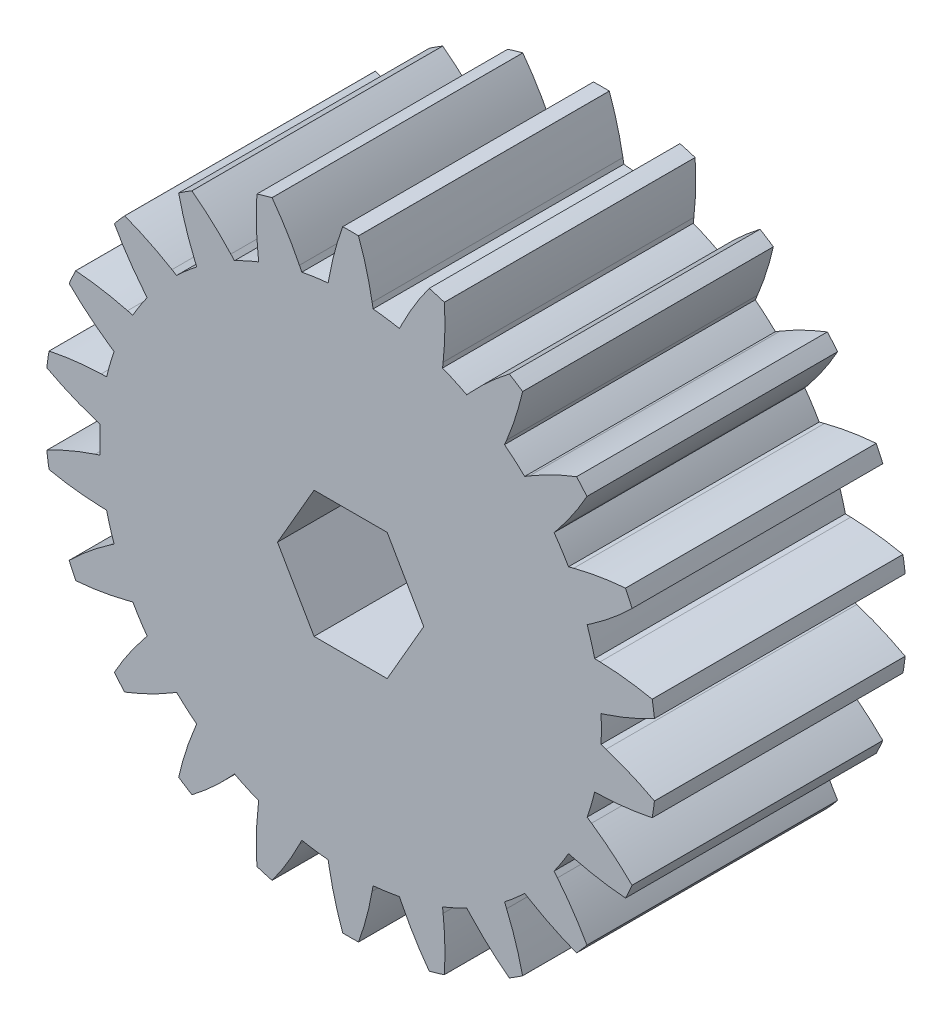
SolidWorks part; units mm, degrees
material "Custom Plastic"
ref_plane "Front Plane" through (0, 0, 0) normal (0, 0, 1) x (1, 0, 0)
ref_plane "Top Plane" through (0, 0, 0) normal (0, 1, 0) x (1, 0, 0)
ref_plane "Right Plane" through (0, 0, 0) normal (1, 0, 0) x (0, 0, -1)
sketch "Sketch1" plane through (0, 0, 0) normal (0, 0, 1) x (1, 0, 0)
  line L0 (0, 30.988) -> (0, 0) construction
  line L1 (-2.2733, 25.2981) -> (-1.27, 30.988)
  line L2 (-1.27, 30.988) -> (1.27, 30.988)
  line L3 (1.27, 30.988) -> (2.2733, 25.2981)
  line L4 (4.9461, 24.9138) -> (7.5118, 30.0906)
  line L5 (7.5118, 30.0906) -> (9.9489, 29.375)
  line L6 (9.9489, 29.375) -> (9.3085, 23.6329)
  line L7 (11.7648, 22.5111) -> (15.685, 26.7554)
  line L8 (15.685, 26.7554) -> (17.8218, 25.3822)
  line L9 (17.8218, 25.3822) -> (15.5896, 20.0531)
  line L10 (17.6303, 18.2847) -> (22.5875, 21.2526)
  line L11 (22.5875, 21.2526) -> (24.2508, 19.333)
  line L12 (24.2508, 19.333) -> (20.6077, 14.8487)
  line L13 (22.0676, 12.5771) -> (27.6601, 14.0281)
  line L14 (27.6601, 14.0281) -> (28.7153, 11.7176)
  line L15 (28.7153, 11.7176) -> (23.9563, 8.4413)
  line L16 (24.717, 5.8504) -> (30.4918, 5.6671)
  line L17 (30.4918, 5.6671) -> (30.8533, 3.153)
  line L18 (30.8533, 3.153) -> (25.3641, 1.3501)
  line L19 (25.3641, -1.3501) -> (30.8533, -3.153)
  line L20 (30.8533, -3.153) -> (30.4918, -5.6671)
  line L21 (30.4918, -5.6671) -> (24.717, -5.8504)
  line L22 (23.9563, -8.4413) -> (28.7153, -11.7176)
  line L23 (28.7153, -11.7176) -> (27.6601, -14.0281)
  line L24 (27.6601, -14.0281) -> (22.0676, -12.5771)
  line L25 (20.6077, -14.8487) -> (24.2508, -19.333)
  line L26 (24.2508, -19.333) -> (22.5875, -21.2526)
  line L27 (22.5875, -21.2526) -> (17.6303, -18.2847)
  line L28 (15.5896, -20.0531) -> (17.8218, -25.3822)
  line L29 (17.8218, -25.3822) -> (15.685, -26.7554)
  line L30 (15.685, -26.7554) -> (11.7648, -22.5111)
  line L31 (9.3085, -23.6329) -> (9.9489, -29.375)
  line L32 (9.9489, -29.375) -> (7.5118, -30.0906)
  line L33 (7.5118, -30.0906) -> (4.9461, -24.9138)
  line L34 (2.2733, -25.2981) -> (1.27, -30.988)
  line L35 (1.27, -30.988) -> (-1.27, -30.988)
  line L36 (-1.27, -30.988) -> (-2.2733, -25.2981)
  line L37 (-4.9461, -24.9138) -> (-7.5118, -30.0906)
  line L38 (-7.5118, -30.0906) -> (-9.9489, -29.375)
  line L39 (-9.9489, -29.375) -> (-9.3085, -23.6329)
  line L40 (-11.7648, -22.5111) -> (-15.685, -26.7554)
  line L41 (-15.685, -26.7554) -> (-17.8218, -25.3822)
  line L42 (-17.8218, -25.3822) -> (-15.5896, -20.0531)
  line L43 (-17.6303, -18.2847) -> (-22.5875, -21.2526)
  line L44 (-22.5875, -21.2526) -> (-24.2508, -19.333)
  line L45 (-24.2508, -19.333) -> (-20.6077, -14.8487)
  line L46 (-22.0676, -12.5771) -> (-27.6601, -14.0281)
  line L47 (-27.6601, -14.0281) -> (-28.7153, -11.7176)
  line L48 (-28.7153, -11.7176) -> (-23.9563, -8.4413)
  line L49 (-24.717, -5.8504) -> (-30.4918, -5.6671)
  line L50 (-30.4918, -5.6671) -> (-30.8533, -3.153)
  line L51 (-30.8533, -3.153) -> (-25.3641, -1.3501)
  line L52 (-25.3641, 1.3501) -> (-30.8533, 3.153)
  line L53 (-30.8533, 3.153) -> (-30.4918, 5.6671)
  line L54 (-30.4918, 5.6671) -> (-24.717, 5.8504)
  line L55 (-23.9563, 8.4413) -> (-28.7153, 11.7176)
  line L56 (-28.7153, 11.7176) -> (-27.6601, 14.0281)
  line L57 (-27.6601, 14.0281) -> (-22.0676, 12.5771)
  line L58 (-20.6077, 14.8487) -> (-24.2508, 19.333)
  line L59 (-24.2508, 19.333) -> (-22.5875, 21.2526)
  line L60 (-22.5875, 21.2526) -> (-17.6303, 18.2847)
  line L61 (-15.5896, 20.0531) -> (-17.8218, 25.3822)
  line L62 (-17.8218, 25.3822) -> (-15.685, 26.7554)
  line L63 (-15.685, 26.7554) -> (-11.7648, 22.5111)
  line L64 (-9.3085, 23.6329) -> (-9.9489, 29.375)
  line L65 (-9.9489, 29.375) -> (-7.5118, 30.0906)
  line L66 (-7.5118, 30.0906) -> (-4.9461, 24.9138)
  arc A0 (-25.3641, 1.3501) -> (-25.3641, -1.3501) centre (0, 0) ccw
  arc A1 (0, 30.988) -> (8.7303, 29.7328) centre (0, 0) cw construction
  arc A2 (-23.9563, 8.4413) -> (-24.717, 5.8504) centre (0, 0) ccw
  arc A3 (-20.6077, 14.8487) -> (-22.0676, 12.5771) centre (0, 0) ccw
  arc A4 (-15.5896, 20.0531) -> (-17.6303, 18.2847) centre (0, 0) ccw
  arc A5 (-9.3085, 23.6329) -> (-11.7648, 22.5111) centre (0, 0) ccw
  arc A6 (-2.2733, 25.2981) -> (-4.9461, 24.9138) centre (0, 0) ccw
  arc A7 (4.9461, 24.9138) -> (2.2733, 25.2981) centre (0, 0) ccw
  arc A8 (11.7648, 22.5111) -> (9.3085, 23.6329) centre (0, 0) ccw
  arc A9 (17.6303, 18.2847) -> (15.5896, 20.0531) centre (0, 0) ccw
  arc A10 (22.0676, 12.5771) -> (20.6077, 14.8487) centre (0, 0) ccw
  arc A11 (24.717, 5.8504) -> (23.9563, 8.4413) centre (0, 0) ccw
  arc A12 (25.3641, -1.3501) -> (25.3641, 1.3501) centre (0, 0) ccw
  arc A13 (23.9563, -8.4413) -> (24.717, -5.8504) centre (0, 0) ccw
  arc A14 (20.6077, -14.8487) -> (22.0676, -12.5771) centre (0, 0) ccw
  arc A15 (15.5896, -20.0531) -> (17.6303, -18.2847) centre (0, 0) ccw
  arc A16 (9.3085, -23.6329) -> (11.7648, -22.5111) centre (0, 0) ccw
  arc A17 (2.2733, -25.2981) -> (4.9461, -24.9138) centre (0, 0) ccw
  arc A18 (-4.9461, -24.9138) -> (-2.2733, -25.2981) centre (0, 0) ccw
  arc A19 (-11.7648, -22.5111) -> (-9.3085, -23.6329) centre (0, 0) ccw
  arc A20 (-17.6303, -18.2847) -> (-15.5896, -20.0531) centre (0, 0) ccw
  arc A21 (-22.0676, -12.5771) -> (-20.6077, -14.8487) centre (0, 0) ccw
  arc A22 (-24.717, -5.8504) -> (-23.9563, -8.4413) centre (0, 0) ccw
  point P102 (0, 0)
  dimension "D3" = 50.8
  dimension "D1" = 2.54
  dimension "D2" = 5.588
  dimension "D4" = 100
  dimension "D6" = 2.7003
  dimension "D7" = 8.8502
  dimension "D5" = 22
extrude "Boss-Extrude1" add sketch "Sketch1" along normal blind 25.4
sketch "Sketch2" plane through (0, 0, 25.4) normal (0, 0, 1) x (1, 0, 0)
  line L0 (1.27, 30.988) -> (-1.27, 30.988) construction
  circle A0 centre (0, 0) radius 30.988
  point P5 (0, 30.988)
extrude "Cut-Extrude1" cut sketch "Sketch2" against normal through all flip side to cut
chamfer "Chamfer1" distance 2.54 angle 10 44 edges at (-22.5646, 21.2389, 12.7) (-24.234, 19.3124, 12.7) (-27.6343, 14.0214, 12.7) (-28.6933, 11.7025, 12.7) (-30.4652, 5.668, 12.7) (-30.828, 3.1447, 12.7) (-30.828, -3.1447, 12.7) (-30.4652, -5.668, 12.7) (-28.6933, -11.7025, 12.7) (-27.6343, -14.0214, 12.7) (-24.234, -19.3124, 12.7) (-22.5646, -21.2389, 12.7) (-17.8115, -25.3576, 12.7) (-15.6669, -26.7358, 12.7) (-9.9459, -29.3485, 12.7) (-7.4999, -30.0667, 12.7) (-1.2746, -30.9618, 12.7) (1.2746, -30.9618, 12.7) (7.4999, -30.0667, 12.7) (9.9459, -29.3485, 12.7) (15.6669, -26.7358, 12.7) (17.8115, -25.3576, 12.7) (22.5646, -21.2389, 12.7) (24.234, -19.3124, 12.7) (27.6343, -14.0214, 12.7) (28.6933, -11.7025, 12.7) (30.4652, -5.668, 12.7) (30.828, -3.1447, 12.7) (30.828, 3.1447, 12.7) (30.4652, 5.668, 12.7) (28.6933, 11.7025, 12.7) (27.6343, 14.0214, 12.7) (24.234, 19.3124, 12.7) (22.5646, 21.2389, 12.7) (17.8115, 25.3576, 12.7) (15.6669, 26.7358, 12.7) (9.9459, 29.3485, 12.7) (7.4999, 30.0667, 12.7) (1.2746, 30.9618, 12.7) (-1.2746, 30.9618, 12.7) (-7.4999, 30.0667, 12.7) (-9.9459, 29.3485, 12.7) (-17.8115, 25.3576, 12.7) (-15.6669, 26.7358, 12.7) first distance on face at (-20.0975, 19.7618, 12.7) first distance on face at (-22.4209, 17.0805, 12.7) first distance on face at (-24.8509, 13.2992, 12.7) first distance on face at (-26.3248, 10.0719, 12.7) first distance on face at (-27.5911, 5.7592, 12.7) first distance on face at (-28.0961, 2.2474, 12.7) first distance on face at (-28.0961, -2.2474, 12.7) first distance on face at (-27.5911, -5.7592, 12.7) first distance on face at (-26.3248, -10.0719, 12.7) first distance on face at (-24.8509, -13.2992, 12.7) first distance on face at (-22.4209, -17.0805, 12.7) first distance on face at (-20.0975, -19.7618, 12.7) first distance on face at (-16.7005, -22.7053, 12.7) first distance on face at (-13.7158, -24.6235, 12.7) first distance on face at (-9.6272, -26.4907, 12.7) first distance on face at (-6.223, -27.4902, 12.7) first distance on face at (-1.774, -28.1299, 12.7) first distance on face at (1.774, -28.1299, 12.7) first distance on face at (6.223, -27.4902, 12.7) first distance on face at (9.6272, -26.4907, 12.7) first distance on face at (13.7158, -24.6235, 12.7) first distance on face at (16.7005, -22.7053, 12.7) first distance on face at (20.0975, -19.7618, 12.7) first distance on face at (22.4209, -17.0805, 12.7) first distance on face at (24.8509, -13.2992, 12.7) first distance on face at (26.3248, -10.0719, 12.7) first distance on face at (27.5911, -5.7592, 12.7) first distance on face at (28.0961, -2.2474, 12.7) first distance on face at (28.0961, 2.2474, 12.7) first distance on face at (27.5911, 5.7592, 12.7) first distance on face at (26.3248, 10.0719, 12.7) first distance on face at (24.8509, 13.2992, 12.7) first distance on face at (22.4209, 17.0805, 12.7) first distance on face at (20.0975, 19.7618, 12.7) first distance on face at (16.7005, 22.7053, 12.7) first distance on face at (13.7158, 24.6235, 12.7) first distance on face at (9.6272, 26.4907, 12.7) first distance on face at (6.223, 27.4902, 12.7) first distance on face at (1.774, 28.1299, 12.7) first distance on face at (-1.774, 28.1299, 12.7) first distance on face at (-6.223, 27.4902, 12.7) first distance on face at (-9.6272, 26.4907, 12.7) first distance on face at (-16.7005, 22.7053, 12.7) first distance on face at (-13.7158, 24.6235, 12.7)
fillet "Fillet1" radius 30.48 44 edges at (-6.372, 27.7909, 12.7) (-13.9435, 24.87, 12.7) (-20.3854, 19.9342, 12.7) (-25.1757, 13.3835, 12.7) (-27.9265, 5.7486, 12.7) (-28.4148, -2.3521, 12.7) (-26.6012, -10.2622, 12.7) (-22.6324, -17.3409, 12.7) (-9.6644, 26.8242, 12.7) (-16.8302, 23.0148, 12.7) (-22.6324, 17.3409, 12.7) (-26.6012, 10.2622, 12.7) (-28.4148, 2.3521, 12.7) (-27.9265, -5.7486, 12.7) (-25.1757, -13.3835, 12.7) (-20.3854, -19.9342, 12.7) (-16.8302, -23.0148, 12.7) (-9.6644, -26.8242, 12.7) (-1.7157, -28.4604, 12.7) (6.372, -27.7909, 12.7) (13.9435, -24.87, 12.7) (-13.9435, -24.87, 12.7) (-6.372, -27.7909, 12.7) (1.7157, -28.4604, 12.7) (9.6644, -26.8242, 12.7) (16.8302, -23.0148, 12.7) (26.6012, 10.2622, 12.7) (28.4148, 2.3521, 12.7) (27.9265, -5.7486, 12.7) (25.1757, -13.3835, 12.7) (20.3854, -19.9342, 12.7) (22.6324, -17.3409, 12.7) (26.6012, -10.2622, 12.7) (28.4148, -2.3521, 12.7) (27.9265, 5.7486, 12.7) (25.1757, 13.3835, 12.7) (-1.7157, 28.4604, 12.7) (6.372, 27.7909, 12.7) (13.9435, 24.87, 12.7) (1.7157, 28.4604, 12.7) (9.6644, 26.8242, 12.7) (16.8302, 23.0148, 12.7) (22.6324, 17.3409, 12.7) (20.3854, 19.9342, 12.7)
sketch "Sketch3" plane through (0, 0, 25.4) normal (0, 0, 1) x (1, 0, 0)
  line L1 (3.7028, 6.4135) -> (-3.7028, 6.4135)
  line L2 (-3.7028, 6.4135) -> (-7.4057, 0)
  line L3 (-7.4057, 0) -> (-3.7028, -6.4135)
  line L4 (-3.7028, -6.4135) -> (3.7028, -6.4135)
  line L5 (3.7028, -6.4135) -> (7.4057, 0)
  line L6 (7.4057, 0) -> (3.7028, 6.4135)
  circle A0 centre (0, 0) radius 6.4135 construction
  dimension "D1" = 12.827
extrude "Cut-Extrude2" cut sketch "Sketch3" against normal up to surface (25.4 mm away) up to face at (0, 0, 0)
